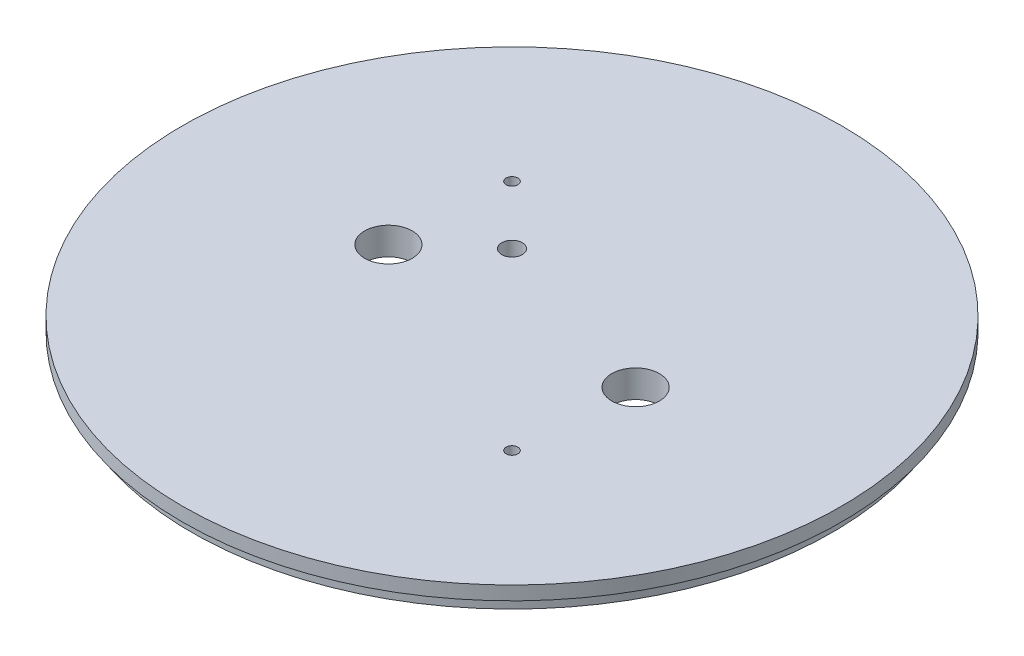
SolidWorks part; units mm, degrees
material "6061-T6 (SS)"
ref_plane "Front Plane" through (0, 0, 0) normal (0, 0, 1) x (1, 0, 0)
ref_plane "Top Plane" through (0, 0, 0) normal (0, 1, 0) x (1, 0, 0)
ref_plane "Right Plane" through (0, 0, 0) normal (1, 0, 0) x (0, 0, -1)
sketch "Sketch1" plane through (0, 0, 0) normal (0, 1, 0) x (1, 0, 0)
  line L0 (0, -76.2) -> (0, 76.2) construction
  line L1 (-76.2, 0) -> (76.2, 0) construction
  line L2 (-26.9408, 26.9408) -> (0, 0) construction
  line L3 (0, 56.7387) -> (0, 29.6936) construction
  line L4 (3.6407, 56.7387) -> (3.6407, 29.6936) construction
  line L5 (-3.6407, 56.7387) -> (-3.6407, 29.6936) construction
  line L6 (0, -56.7387) -> (0, -29.6936) construction
  line L7 (3.6407, -56.7387) -> (3.6407, -29.6936) construction
  line L8 (-3.6407, -56.7387) -> (-3.6407, -29.6936) construction
  line L9 (-53.8815, -53.8815) -> (54.3236, 54.3236) construction
  circle A0 centre (0, 0) radius 76.2
  circle A1 centre (0, 0) radius 3.175 construction
  circle A2 centre (28.575, 0) radius 5.5
  circle A3 centre (-28.575, 0) radius 5.5
  circle A4 centre (-26.9408, 26.9408) radius 1.3589
  arc A6 (3.6407, 56.7387) -> (-3.6407, 56.7387) centre (0, 56.7387) ccw construction
  arc A7 (-3.6407, 29.6936) -> (3.6407, 29.6936) centre (0, 29.6936) ccw construction
  arc A8 (3.6407, -56.7387) -> (-3.6407, -56.7387) centre (0, -56.7387) cw construction
  arc A9 (-3.6407, -29.6936) -> (3.6407, -29.6936) centre (0, -29.6936) cw construction
  circle A10 centre (26.9408, -26.9408) radius 1.3589
  circle A11 centre (-13.4704, 13.4704) radius 2.3813
  point P16 (0, 43.2162)
  point P19 (0, 0)
  point P26 (0, -43.2162)
  dimension "D1" = 152.4
  dimension "D2" = 6.35
  dimension "D3" = 11
  dimension "D5" = 2.7178
  dimension "D8" = 4.7625
  dimension "D6" = 38.1
  dimension "D7" = 45
  dimension "D4" = 45
  dimension "D9" = 28.575
extrude "Boss-Extrude1" add sketch "Sketch1" along normal blind 6.35
sketch "Sketch2" plane through (0, 0, 0) normal (0, -1, 0) x (1, 0, 0)
  circle A0 centre (0, 0) radius 76.2
  circle A1 centre (0, 0) radius 74.041
  dimension "D1" = 152.4
  dimension "D2" = 148.082
extrude "Cut-Extrude1" cut sketch "Sketch2" against normal blind 3.175
sketch "Sketch3" plane through (0, 6.35, 0) normal (0, 1, 0) x (1, 0, 0)
  line L0 (0, 76.2) -> (0, -76.2) construction
  line L1 (-76.2, 0) -> (76.2, 0) construction
  line L2 (0, 34.798) -> (0, 13.97) construction
  line L3 (3.2385, 34.798) -> (3.2385, 13.97)
  line L4 (-3.2385, 34.798) -> (-3.2385, 13.97)
  line L5 (0, -34.798) -> (0, -13.97) construction
  line L6 (3.2385, -34.798) -> (3.2385, -13.97)
  line L7 (-3.2385, -34.798) -> (-3.2385, -13.97)
  circle A0 centre (0, 0) radius 76.2 construction
  arc A1 (3.2385, 34.798) -> (-3.2385, 34.798) centre (0, 34.798) ccw
  arc A2 (-3.2385, 13.97) -> (3.2385, 13.97) centre (0, 13.97) ccw
  arc A3 (3.2385, -34.798) -> (-3.2385, -34.798) centre (0, -34.798) cw
  arc A4 (-3.2385, -13.97) -> (3.2385, -13.97) centre (0, -13.97) cw
  point P7 (0, 13.97)
  point P8 (0, 34.798)
  point P12 (0, 24.384)
  point P20 (0, -24.384)
  point P25 (0, -34.798)
  point P26 (0, -13.97)
  dimension "D1" = 13.97
  dimension "D2" = 20.828
  dimension "D3" = 6.477
extrude "Cut-Extrude2" cut sketch "Sketch3" against normal blind 3.556 from offset 5.969 offset against normal yes
equation "\"leadDist\"=1.5"
equation "\"Lead_Screw_Dist\" = 2.25in"
equation "\"D9@Sketch1\"=\"Lead_Screw_Dist\"/2"
equation "\"Lead_Screw_Diam\" = 11mm"
equation "\"D3@Sketch1\"=\"Lead_Screw_Diam\""
